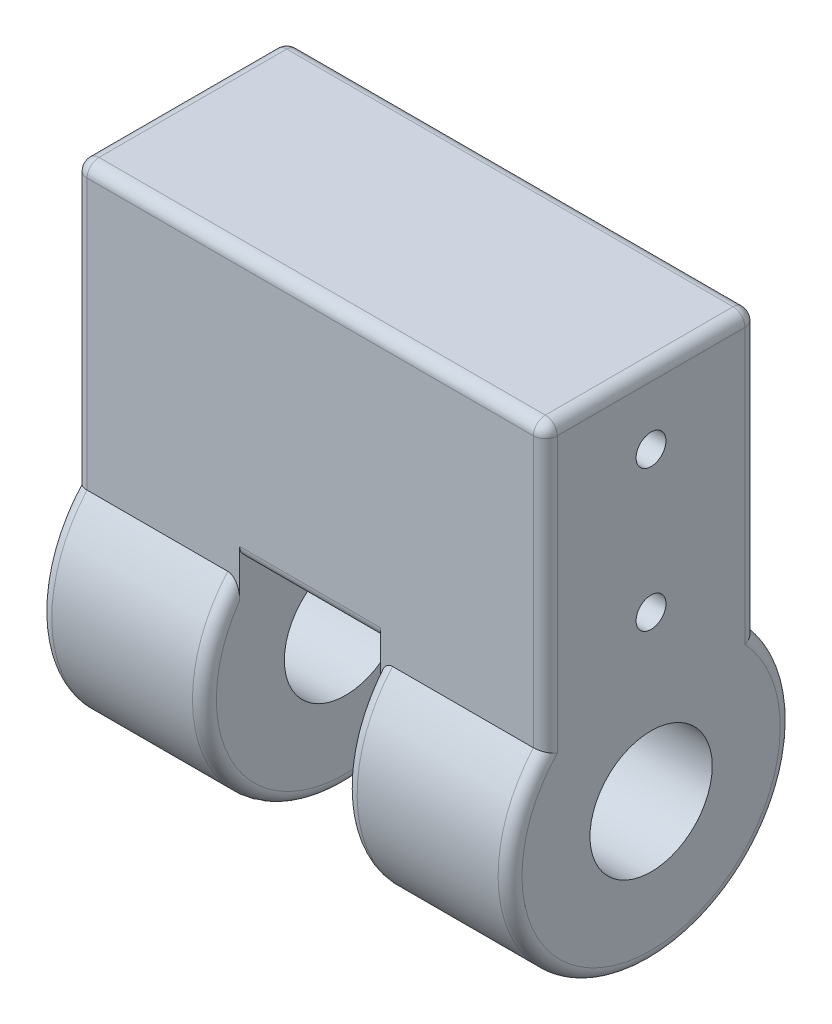
SolidWorks part; units mm, degrees
ref_plane "Front Plane" through (0, 0, 0) normal (0, 0, 1) x (1, 0, 0)
ref_plane "Top Plane" through (0, 0, 0) normal (0, 1, 0) x (1, 0, 0)
ref_plane "Right Plane" through (0, 0, 0) normal (1, 0, 0) x (0, 0, -1)
sketch "Sketch1" plane through (0, 0, 0) normal (1, 0, 0) x (0, 0, -1)
  line L0 (0, 13) -> (0, -30) construction
  line L3 (-22.5, 19.8431) -> (-22.5, 79.8431)
  line L4 (-22.5, 79.8431) -> (22.5, 79.8431)
  line L5 (22.5, 19.8431) -> (22.5, 79.8431)
  arc A0 (-22.5, 19.8431) -> (22.5, 19.8431) centre (0, 0) ccw
  circle A1 centre (0, 0) radius 13
  point P6 (-22.5, 19.8431)
  point P7 (22.5, 19.8431)
  dimension "D1" = 26
  dimension "D2" = 60
  dimension "D3" = 60
  dimension "D4" = 45
extrude "Boss-Extrude1" add sketch "Sketch1" along normal blind 100
sketch "Sketch2" plane through (0, 0, 0) normal (0, 0, 1) x (1, 0, 0)
  line L0 (64.948, 79.8431) -> (64.948, -40.1569) construction
  line L1 (35, 79.8431) -> (35, -40.1569) construction
  line L2 (100, -40.1569) -> (0, -40.1569) construction
  line L4 (0, 79.8431) -> (0, 19.8431)
  line L5 (100, 79.8431) -> (0, 79.8431)
  line L6 (100, 19.8431) -> (100, 79.8431)
  line L7 (0, 19.8431) -> (100, 19.8431)
  line L8 (0, 79.8431) -> (0, -40.1569) construction
  line L9 (100, 79.8431) -> (0, 79.8431) construction
  line L10 (100, -40.1569) -> (100, 79.8431) construction
  line L11 (0, 19.8431) -> (100, 19.8431) construction
  line L12 (64.948, 19.8431) -> (35, 19.8431)
  line L13 (64.948, 19.8431) -> (64.948, -40.1569)
  line L14 (64.948, -40.1569) -> (35, -40.1569)
  line L15 (35, 19.8431) -> (35, -40.1569)
  point P10 (35, 19.8431)
  point P12 (64.948, 19.8431)
  dimension "D2" = 35
  dimension "D3" = 35.052
  dimension "D1" = 0
extrude "Cut-Extrude1" cut sketch "Sketch2" along normal blind 90 and the other way blind 90
sketch "Sketch3" plane through (64.948, 0, 0) normal (-1, 0, 0) x (0, 0, 1)
  circle A0 centre (0, 0) radius 30
  dimension "D1" = 60
extrude "Cut-Extrude2" cut sketch "Sketch3" along normal up to surface (29.948 mm away) up to face at (35, 0, 13)
sketch "Sketch4" plane through (100, 0, 0) normal (1, 0, 0) x (0, 0, -1)
  circle A0 centre (-0.021, 34.8431) radius 3.175
  circle A3 centre (-0.021, 64.8431) radius 3.175
  dimension "D2" = 6.35
  dimension "D3" = 30
extrude "Cut-Extrude3" cut sketch "Sketch4" against normal through all
fillet "Fillet3" radius 2.54 12 edges at (0, 49.8431, -22.5) (0, 79.8431, 0) (50, 79.8431, -22.5) (0, 49.8431, 22.5) (50, 79.8431, 22.5) (100, 79.8431, 0) (100, 49.8431, -22.5) (100, 49.8431, 22.5) (0, -30, 0) (100, -30, 0) (35, -30, 0) (64.948, -30, 0)
fillet "Fillet4" radius 2.54 2 edges at (49.974, 19.8431, -22.5) (49.974, 19.8431, 22.5)
